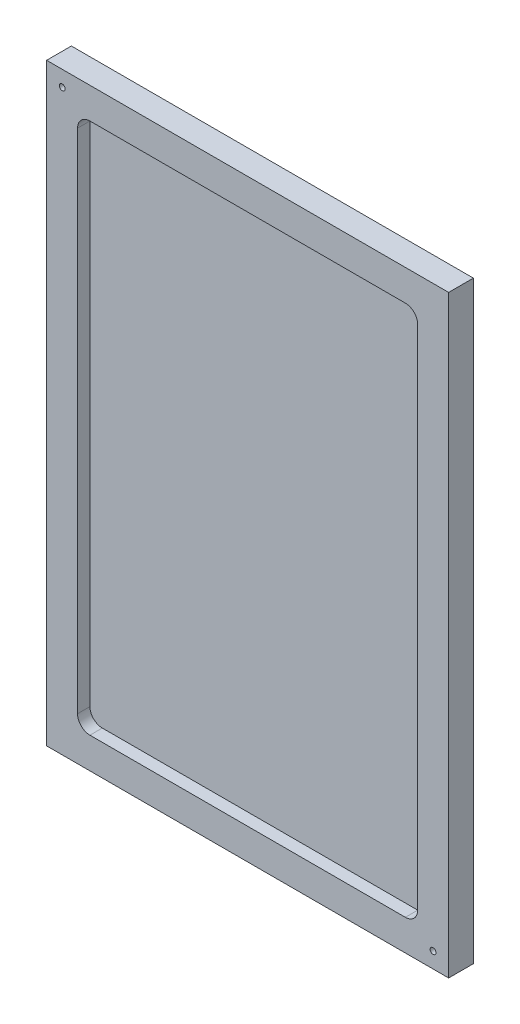
SolidWorks part; units mm, degrees
ref_plane "Front Plane" through (0, 0, 0) normal (0, 0, 1) x (1, 0, 0)
ref_plane "Top Plane" through (0, 0, 0) normal (0, 1, 0) x (1, 0, 0)
ref_plane "Right Plane" through (0, 0, 0) normal (1, 0, 0) x (0, 0, -1)
sketch "Sketch1" plane through (0, 0, 0) normal (0, 0, 1) x (1, 0, 0)
  line L1 (103.1875, -152.4) -> (-103.1875, -152.4)
  line L2 (103.1875, -152.4) -> (103.1875, 152.4)
  line L3 (103.1875, 152.4) -> (-103.1875, 152.4)
  line L4 (-103.1875, -152.4) -> (-103.1875, 152.4)
  line L5 (103.1875, -152.4) -> (-103.1875, 152.4) construction
  line L6 (103.1875, 152.4) -> (-103.1875, -152.4) construction
  point P0 (0, 0)
  dimension "D1" = 304.8
  dimension "D2" = 206.375
extrude "Boss-Extrude1" add sketch "Sketch1" along normal blind 12.7
sketch "Sketch2" plane through (0, 0, 12.7) normal (0, 0, 1) x (1, 0, 0)
  line L0 (-103.1875, 152.4) -> (-103.1875, -152.4) construction
  line L1 (80.9625, -136.525) -> (-80.9625, -136.525)
  line L2 (87.3125, -130.175) -> (87.3125, 130.175)
  line L3 (80.9625, 136.525) -> (-80.9625, 136.525)
  line L4 (-87.3125, -130.175) -> (-87.3125, 130.175)
  line L5 (87.3125, -136.525) -> (-87.3125, 136.525) construction
  line L6 (87.3125, 136.525) -> (-87.3125, -136.525) construction
  line L7 (103.1875, 152.4) -> (-103.1875, 152.4) construction
  arc A0 (-80.9625, -136.525) -> (-87.3125, -130.175) centre (-80.9625, -130.175) cw
  arc A1 (80.9625, -136.525) -> (87.3125, -130.175) centre (80.9625, -130.175) ccw
  arc A2 (87.3125, 130.175) -> (80.9625, 136.525) centre (80.9625, 130.175) ccw
  arc A3 (-80.9625, 136.525) -> (-87.3125, 130.175) centre (-80.9625, 130.175) ccw
  point P0 (0, 0)
  dimension "D3" = 6.35
  dimension "D1" = 15.875
  dimension "D2" = 15.875
extrude "Cut-Extrude1" cut sketch "Sketch2" against normal blind 6.35
sketch "Sketch3" plane through (0, 0, 12.7) normal (0, 0, 1) x (1, 0, 0)
  line L0 (95.6521, -142.2937) -> (97.3079, -144.7953) construction
  line L1 (94.7229, -146.5063) -> (93.0671, -144.0047) construction
  line L2 (95.6521, -142.2937) -> (97.3079, -144.7953) construction
  line L3 (94.7229, -146.5063) -> (93.0671, -144.0047) construction
  circle A0 centre (-95.1875, 144.4) radius 1.55 construction
  arc A1 (95.6521, -142.2937) -> (93.0671, -144.0047) centre (94.3596, -143.1492) ccw construction
  arc A2 (94.7229, -146.5063) -> (97.3079, -144.7953) centre (96.0154, -145.6508) ccw construction
  circle A3 centre (-95.1875, 144.4) radius 1.55 construction
  arc A4 (95.6521, -142.2937) -> (93.0671, -144.0047) centre (94.3596, -143.1492) ccw construction
  arc A5 (94.7229, -146.5063) -> (97.3079, -144.7953) centre (96.0154, -145.6508) ccw construction
hole_wizard "Ø3.0 (3) Diameter Hole1" positions "3DSketch1" profile "Sketch4" hole size "Ø3.0" standard "ANSI Metric"
sketch3d "3DSketch1"
  line L0 (-103.1875, -152.4, 12.7) -> (103.1875, -152.4, 12.7) construction
  line L1 (103.1875, -152.4, 12.7) -> (103.1875, 152.4, 12.7) construction
  line L2 (-103.1875, 152.4, 12.7) -> (-103.1875, -152.4, 12.7) construction
  line L3 (103.1875, 152.4, 12.7) -> (-103.1875, 152.4, 12.7) construction
  point P0 (-95.1875, 144.4, 12.7)
  point P2 (95.1875, -144.4, 12.7)
  dimension "D1" = 8
  dimension "D2" = 8
  dimension "D3" = 8
  dimension "D4" = 8
sketch "Sketch4" plane through (-95.1875, 144.4, 12.7) normal (1, 0, 0) x (0, -1, 0)
  line L0 (0, 0) -> (0, 5.9013)
  line L1 (0, 5.9013) -> (1.5, 5)
  line L2 (1.5, 5) -> (1.5, 0)
  line L5 (1.5, 0) -> (0, 0)
  line L10 (0, 5.9013) -> (-1.5, 5) construction
  line L11 (0, -6.35) -> (0, 107.95) construction
  dimension "Hole Dia." = 3
  dimension "Hole Depth" = 5
  dimension "Drill Angle" = 118
